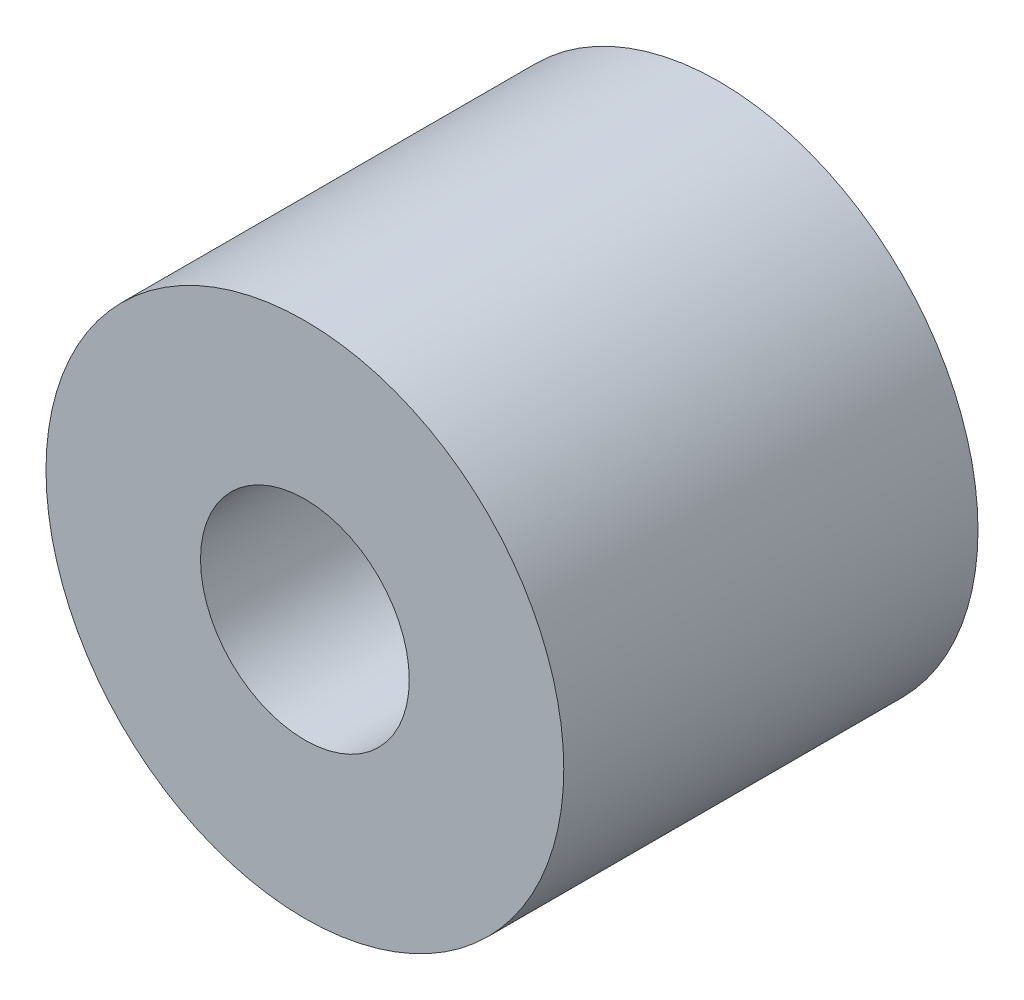
SolidWorks part; units mm, degrees
ref_plane "Front Plane" through (0, 0, 0) normal (0, 0, 1) x (1, 0, 0)
ref_plane "Top Plane" through (0, 0, 0) normal (0, 1, 0) x (1, 0, 0)
ref_plane "Right Plane" through (0, 0, 0) normal (1, 0, 0) x (0, 0, -1)
sketch "Sketch1" plane through (0, 0, 0) normal (0, 0, 1) x (1, 0, 0)
  circle A0 centre (0, 0) radius 7.9375
  circle A1 centre (0, 0) radius 3.2004
  dimension "OD" = 15.875
  dimension "ID" = 6.4008
extrude "Extrude1" add sketch "Sketch1" along normal mid plane 12.7
sketch "Sketch2" plane through (0, 0, 0) normal (1, 0, 0) x (0, 0, -1)
  line L0 (-6.35, -3.2004) -> (6.35, -3.2004) construction
  line L3 (6.35, 3.2004) -> (-6.35, 3.2004) construction
  line L5 (-6.35, -3.2004) -> (6.35, -3.2004)
  line L6 (6.35, 3.2004) -> (-6.35, 3.2004)
sketch "Sketch4" plane through (0, 0, 6.35) normal (0, 0, 1) x (1, 0, 0)
  line L0 (0, 0) -> (-2.263, 2.263)
  line L1 (0, -2.1828) -> (0, 2.1828) construction
  circle A0 centre (0, 0) radius 3.2004 construction
  dimension "D1" = 45
ref_axis "Axis1" through (0, 0, 6.35) along (0, 0, -1)
